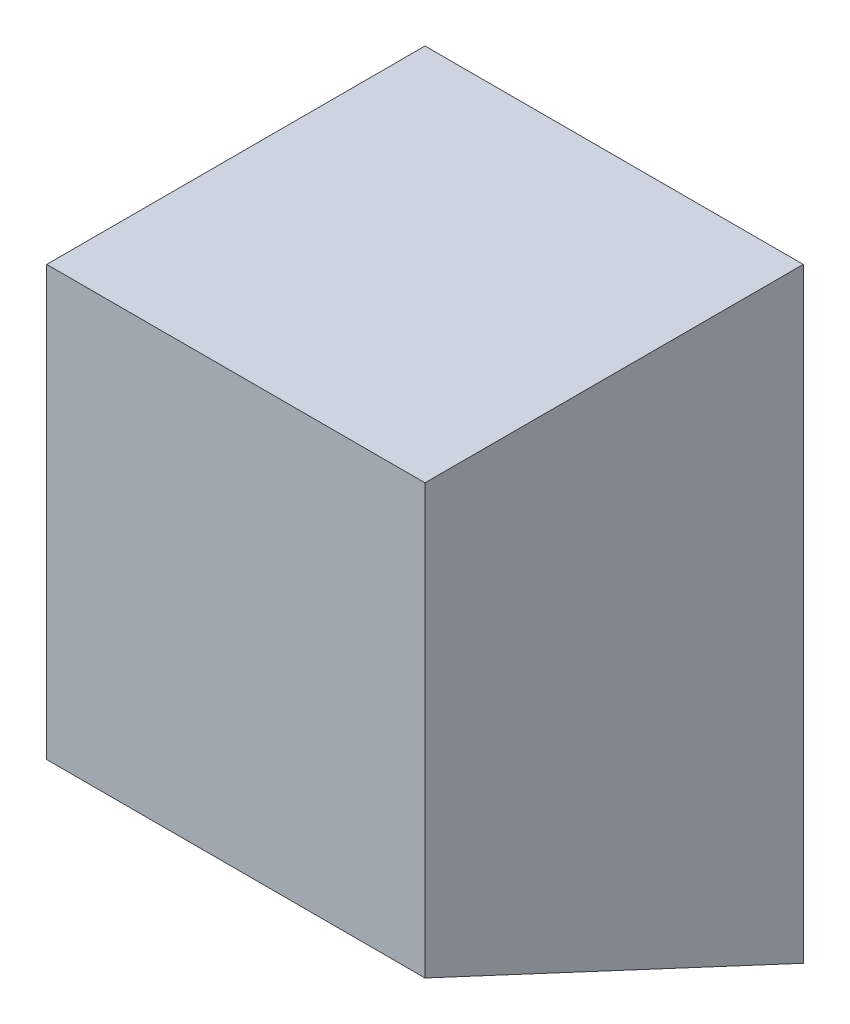
SolidWorks part; units mm, degrees
material "ABS"
ref_plane "Front Plane" through (0, 0, 0) normal (0, 0, 1) x (1, 0, 0)
ref_plane "Top Plane" through (0, 0, 0) normal (0, 1, 0) x (1, 0, 0)
ref_plane "Right Plane" through (0, 0, 0) normal (1, 0, 0) x (0, 0, -1)
sketch "Sketch1" plane through (0, 0, 0) normal (0, 1, 0) x (1, 0, 0)
  line L1 (-76.9048, 16.0714) -> (-51.9048, 16.0714)
  line L2 (-76.9048, 16.0714) -> (-76.9048, -8.9286)
  line L3 (-76.9048, -8.9286) -> (-51.9048, -8.9286)
  line L4 (-51.9048, 16.0714) -> (-51.9048, -8.9286)
  dimension "D1" = 25
  dimension "D2" = 25
extrude "Boss-Extrude1" add sketch "Sketch1" along normal blind 40
sketch "Sketch2" plane through (-51.9048, 0, 0) normal (1, 0, 0) x (0, 0, -1)
  line L3 (-8.9286, 0) -> (16.0714, 0) construction
  line L5 (16.0714, 0) -> (-8.9286, 0)
  line L6 (16.0714, 40) -> (16.0714, 0) construction
  line L7 (-8.9286, 40) -> (-8.9286, 0) construction
  line L8 (-8.9286, 0) -> (-8.9286, 11.6577)
  line L9 (-8.9286, 11.6577) -> (16.0714, 0)
  dimension "D1" = 25
  dimension "D2" = 0
extrude "Cut-Extrude1" cut sketch "Sketch2" against normal blind 40
